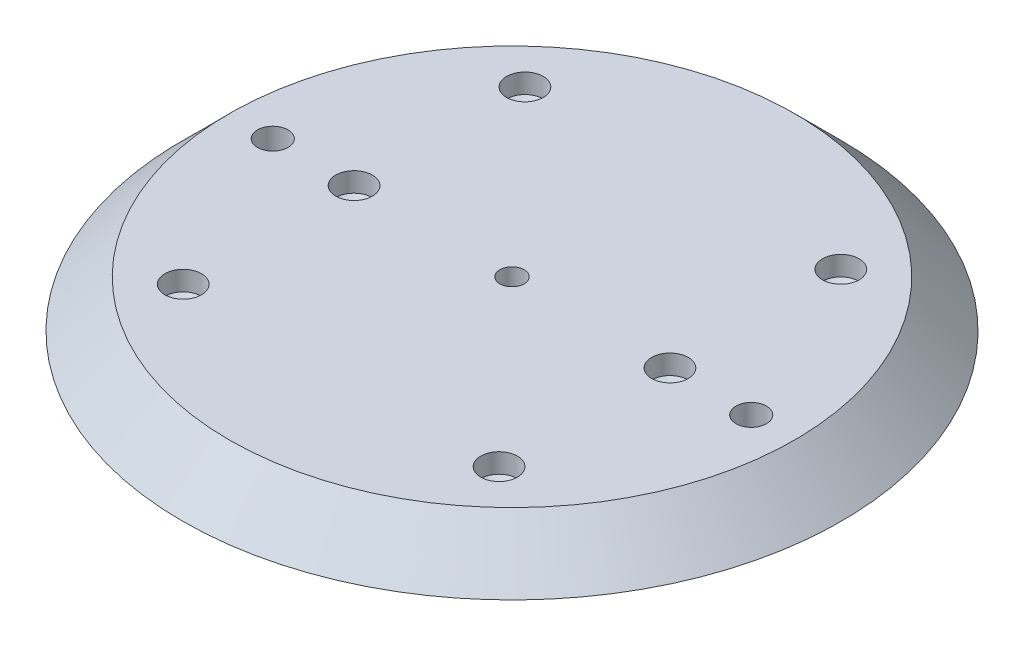
SolidWorks part; units mm, degrees
material "Malleable Cast Iron"
ref_plane "Front Plane" through (0, 0, 0) normal (0, 0, 1) x (1, 0, 0)
ref_plane "Top Plane" through (0, 0, 0) normal (0, 1, 0) x (1, 0, 0)
ref_plane "Right Plane" through (0, 0, 0) normal (1, 0, 0) x (0, 0, -1)
sketch "Sketch10" plane through (0, 0, 0) normal (0, 1, 0) x (1, 0, 0)
  line B0 (-31.369, -69.0517) -> (-31.369, 69.0517) construction
  line B1 (50.8, -69.0517) -> (50.8, 69.0517) construction
  line B2 (-50.8, -69.0517) -> (-50.8, 69.0517) construction
  line B3 (50.8, 69.0517) -> (-50.8, 69.0517) construction
  line B4 (31.369, 69.0517) -> (31.369, -69.0517) construction
  circle B5 centre (0, 0) radius 85.725
  line B6 (-31.369, 0) -> (31.369, 0) construction
  line B7 (41.0845, -69.0517) -> (41.0845, 69.0517) construction
  line B8 (31.369, 0) -> (50.8, 0) construction
  line B9 (-31.369, 0) -> (-50.8, 0) construction
  line B10 (-41.0845, 44.45) -> (41.0845, -44.45) construction
  line B11 (-41.0845, -69.0517) -> (-41.0845, 69.0517) construction
  line B12 (-41.0845, -44.45) -> (41.0845, 44.45) construction
  line B13 (-50.8, 0) -> (-85.725, 0) construction
  line B14 (50.8, 0) -> (85.725, 0) construction
  line B15 (0, -85.725) -> (0, 85.725) construction
sketch_block_instance "swivel plate-1"
sketch_block "swivel plate" parameters "D1"=171.45, "D2"=32.9884, "D3"=88.1371, "D4"=89.3617, "D5"=152.4754
sketch "Sketch1" plane through (0, 0, 0) normal (0, 1, 0) x (1, 0, 0)
  circle A0 centre (0, 0) radius 85.725 construction
  circle A1 centre (0, 0) radius 85.725
extrude "Boss-Extrude1" add sketch "Sketch1" along normal blind 12.192 draft 45
hole_wizard "3/8-16 Tapped Hole1" positions "Sketch6" profile "Sketch7" tap size "3/8-16" standard "ANSI Inch" end condition through all
sketch "Sketch6" plane through (0, 12.192, 0) normal (0, 1, 0) x (-0.9997, 0, -0.0242)
  point P13 (62.2117, 1.5089)
  point P15 (-62.2117, -1.5089)
sketch "Sketch7" plane through (-62.23, 12.192, 0) normal (1, 0, 0) x (0, 0, 1)
  line L0 (0, 0) -> (0, 12.192)
  line L1 (0, 12.192) -> (3.9687, 12.192)
  line L2 (3.9687, 12.192) -> (3.9687, 0)
  line L5 (3.9687, 0) -> (0, 0)
  line L11 (0, -6.35) -> (0, 107.95) construction
  dimension "Thru Tap Drill Dia." = 7.9375
  dimension "Thru Tap Drill Depth" = 12.192
cosmetic thread "Hole Thread1"
cosmetic thread "Hole Thread2"
hole_wizard "1/4 (0.25) Press Dowel Hole1" positions "Sketch8" profile "Sketch9" hole size "1/4" standard "ANSI Inch" end condition through all
sketch "Sketch8" plane through (-177.9915, 12.192, 193.466) normal (0, 1, 0) x (-0.9096, 0, -0.4155)
  point P2 (-81.5106, -249.9322)
sketch "Sketch9" plane through (0, 12.192, 0) normal (1, 0, 0) x (0, 0, 1)
  line L0 (0, 0) -> (0, 12.192)
  line L1 (0, 12.192) -> (3.175, 12.192)
  line L2 (3.175, 12.192) -> (3.175, 0)
  line L3 (3.175, 0) -> (0, 0)
  line L4 (0, -6.35) -> (0, 107.95) construction
  dimension "Thru Hole Dia." = 6.35
  dimension "Thru Hole Depth" = 12.192
hole_wizard "3/8 (0.375) Diameter Hole1" positions "Sketch12" profile "Sketch11" hole size "3/8" standard "ANSI Inch"
sketch "Sketch12" plane through (0, 12.192, 0) normal (0, 1, 0) x (1, 0, 0)
  point P4 (-41.0845, 44.45)
  point P6 (-41.0845, 0)
  point P8 (-41.0845, -44.45)
  point P10 (41.0845, -44.45)
  point P12 (41.0845, 0)
  point P14 (41.0845, 44.45)
sketch "Sketch11" plane through (-41.0845, 12.192, -44.45) normal (1, 0, 0) x (0, 0, 1)
  line L0 (0, 0) -> (0, 7.9416)
  line L1 (0, 7.9416) -> (4.7625, 5.08)
  line L2 (4.7625, 5.08) -> (4.7625, 0)
  line L5 (4.7625, 0) -> (0, 0)
  line L10 (0, 7.9416) -> (-4.7625, 5.08) construction
  line L11 (0, -6.35) -> (0, 107.95) construction
  dimension "Hole Dia." = 9.525
  dimension "Hole Depth" = 5.08
  dimension "Drill Angle" = 118
equation "\"delta-z\"= 1.5"
equation "\"total-height\"= 3.28"
equation "\"mid-height\"= 1.5"
equation "\"jaw-width\"= 4"
equation "\"jaw-height\"= \"total-height\" - \"mid-height\""
equation "\"max-tube-diam\"= 3.5"
equation "\"v-block-notch-height\"= 1.5"
equation "\"v-block-notch-angle\"= 120"
equation "\"jaw-travel\"= 4.45"
equation "\"rib-top-width\"= 0.5"
equation "\"rib-side-width\"= 0.5"
equation "\"quarter-twenty-close-clearance\"= .257"
equation "\"box-way-width\"= 1.5"
equation "\"box-way-depth\"= 1.5"
equation "\"screw-OD\"= .625"
equation "\"screw-reduced-diam\"= .47"
equation "\"pressure-plate-OD\"= 6.75"
equation "\"swivel-cleat-thick\"= .5"
equation "\"swivel-gap\"= .02"
equation "\"D1@Boss-Extrude1\"=\"swivel-cleat-thick\" - \"swivel-gap\""
equation "\"D1@swivel plate\"=\"pressure-plate-OD\""
equation "\"D2@swivel plate\"=\"jaw-width\""
equation "\"D3@swivel plate\"=2.47"
